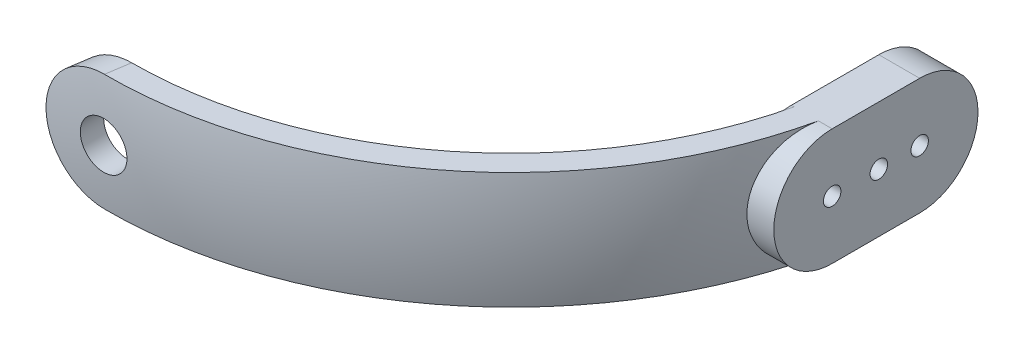
SolidWorks part; units mm, degrees
note: '?' marks a value the reader was unsure of.
ref_plane "前视基准面" through (0, 0, 0) normal (0, 0, 1) x (1, 0, 0)
ref_plane "上视基准面" through (0, 0, 0) normal (0, 1, 0) x (1, 0, 0)
ref_plane "右视基准面" through (0, 0, 0) normal (1, 0, 0) x (0, 0, -1)
ref_plane "基准面1" through (70, 0, 0) normal (1, 0, 0) x (0, 0, -1)
sketch "草图2" plane through (0, 0, 0) normal (0, 0, 1) x (1, 0, 0)
  line L0 (0, 0) -> (70, 0) construction
  line L1 (65.238, 10) -> (69.282, 10)
  line L2 (0, 0) -> (0, 18.8305) construction
  line L3 (69.282, -10) -> (65.238, -10)
  arc A0 (65.238, -10) -> (65.238, 10) centre (0, 0) ccw
  arc A1 (69.282, -10) -> (69.282, 10) centre (0, 0) ccw
  dimension "D1" = 10
  dimension "D3" = 66
  dimension "D4" = 70
  dimension "D2" = 10
revolve "旋转1" add sketch "草图2" angle 98.681 about L2
ref_plane "基准面2" through (63, 0, 0) normal (1, 0, 0) x (0, 0, -1)
sketch "草图3" plane through (0, 0, 0) normal (0, 0, 1) x (1, 0, 0)
  circle A0 centre (0, 0) radius 4
extrude "切除-拉伸1" cut sketch "草图3" along normal through all
sketch "草图4" plane through (0, 0, 0) normal (1, 0, 0) x (0, 0, -1)
  circle A0 centre (0, 0) radius 1.5
extrude "切除-拉伸2" cut sketch "草图4" along normal through all
sketch "草图7" plane through (63, 0, 0) normal (1, 0, 0) x (0, 0, -1)
  line L1 (25, -10) -> (-15, -10)
  line L2 (25, -10) -> (25, 10)
  line L3 (25, 10) -> (-15, 10)
  line L5 (25, -10) -> (-25, 10) construction
  line L6 (25, 10) -> (-25, -10) construction
  arc A0 (-15, 10) -> (-15, -10) centre (-15, 0) ccw
  point P0 (0, 0)
  dimension "D3" = 15
  dimension "D4" = 20
  dimension "D1" = 20
  dimension "D2" = 50
extrude "切除-拉伸3" cut sketch "草图7" along normal through all
ref_axis "基准轴1" through (-15.2008, 0, 0) along (1, 0, 0)?
ref_axis "基准轴2" through (0, 0, -15.1951) along (0, 0, 1)?
fillet "圆角1" radius 10 2 edges at (-10.152, 10, 66.4895) (-10.152, -10, 66.4895)
sketch "草图8" plane through (70, 0, 0) normal (1, 0, 0) x (0, 0, -1)
  line L3 (15.1951, 0) -> (-73.9371, 0) construction
  line L4 (-15, 10) -> (0, 10)
  line L5 (-15, -10) -> (0, -10)
  circle A6 centre (0, 0) radius 1.5
  circle A7 centre (-7, 0) radius 1.5
  circle A8 centre (-15, 0) radius 1.5
  arc A9 (0, -10) -> (0, 10) centre (0, 0) ccw
  arc A10 (-15, 10) -> (-15, -10) centre (-15, 0) ccw
  point P9 (-44.974, 2.7274)
  dimension "D1" = 7
  dimension "D2" = 15
  dimension "D3" = 10
extrude "凸台-拉伸1" add sketch "草图8" against normal blind 7
